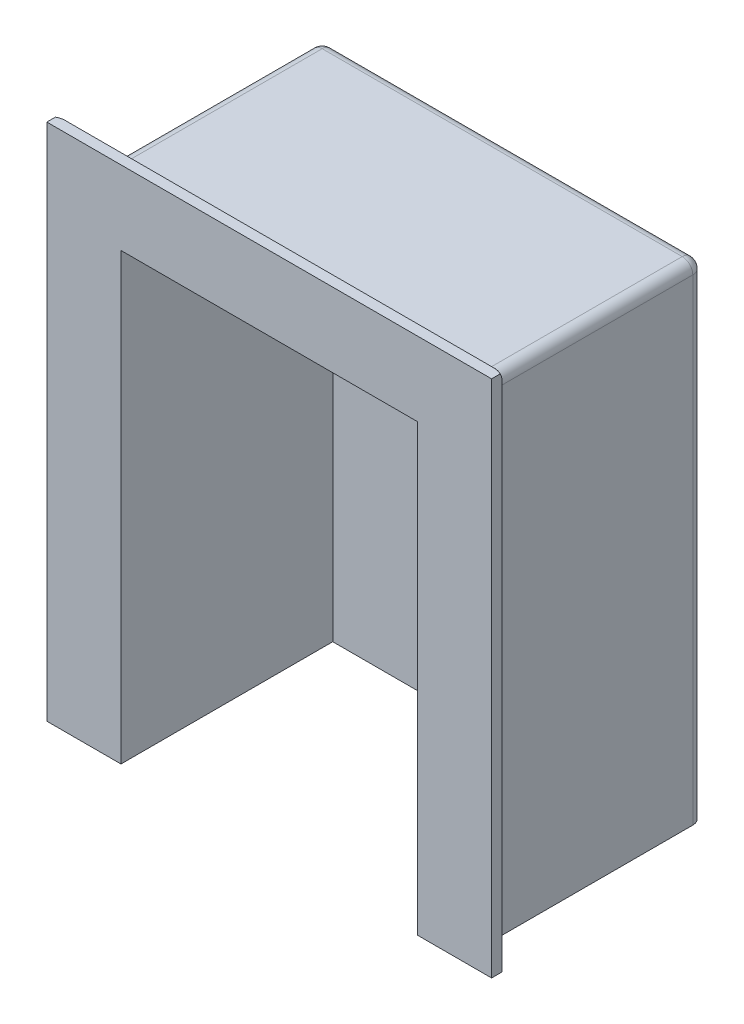
SolidWorks part; units mm, degrees
note: The reader was unsure of these and kept them because the rebuilt part matched: shared geometry of "Sketch1<4>".
ref_plane "Front Plane" through (0, 0, 0) normal (0, 0, 1) x (1, 0, 0)
ref_plane "Top Plane" through (0, 0, 0) normal (0, 1, 0) x (1, 0, 0)
ref_plane "Right Plane" through (0, 0, 0) normal (1, 0, 0) x (0, 0, -1)
sketch "Sketch1" plane through (0, 0, 0) normal (0, 0, 1) x (1, 0, 0)
  line L0 (-9, -12.5) -> (-9, 12.5)
  line L1 (-7, -10.5) -> (7, -10.5)
  line L2 (-7, -10.5) -> (-7, 10.5)
  line L3 (-7, 10.5) -> (7, 10.5)
  line L4 (7, -10.5) -> (7, 10.5)
  line L5 (-7, -10.5) -> (7, 10.5) construction
  line L6 (-7, 10.5) -> (7, -10.5) construction
  line L7 (-9, 12.5) -> (9, 12.5)
  line L8 (9, -12.5) -> (9, 12.5)
  line L9 (-9, -12.5) -> (9, -12.5)
  line L10 (-7, -10.5) -> (-9, -10.5)
  line L11 (7, -10.5) -> (9, -10.5)
  point P0 (0, 0)
  dimension "D1" = 14
  dimension "D2" = 21
  dimension "D3" = 2
extrude "Boss-Extrude1" add sketch "Sketch1" along normal blind 1.5 contours L1 L4 L3 L2
extrude "Boss-Extrude2" add sketch "Sketch1<4>" along normal blind 11.5 contours L4 L11 L8 L7 L0 L10 L2 L3
sketch "Sketch1<4>" plane through (0, 0, 0) normal (0, 0, 1) x (1, 0, 0) same geometry as "Sketch1"
sketch "Sketch2" plane through (0, 0, 11.5) normal (0, 0, 1) x (1, 0, 0)
  line L0 (-9, -10.5) -> (-9, 12.5)
  line L1 (-9, 12.5) -> (9, 12.5)
  line L3 (9, 12.5) -> (9, -10.5)
  line L4 (-10.5, -10.5) -> (-10.5, 14)
  line L5 (-10.5, 14) -> (10.5, 14)
  line L6 (10.5, 14) -> (10.5, -10.5)
  line L7 (-10.5, -10.5) -> (-9, -10.5)
  line L8 (9, -10.5) -> (10.5, -10.5)
  dimension "D1" = 1.5
extrude "Boss-Extrude3" add sketch "Sketch2" against normal blind 0.5
chamfer "Chamfer1" distance 1.5 angle 45 3 edges at (-9, 1, 11) (0, 12.5, 11) (9, 1, 11)
fillet "Fillet1" radius 0.5 7 edges at (-9.75, 13.25, 10.25) (9.75, 13.25, 10.25) (9, 12.5, 4.75) (-9, 12.5, 4.75) (-9, 1, 0) (9, 1, 0) (0, 12.5, 0)
